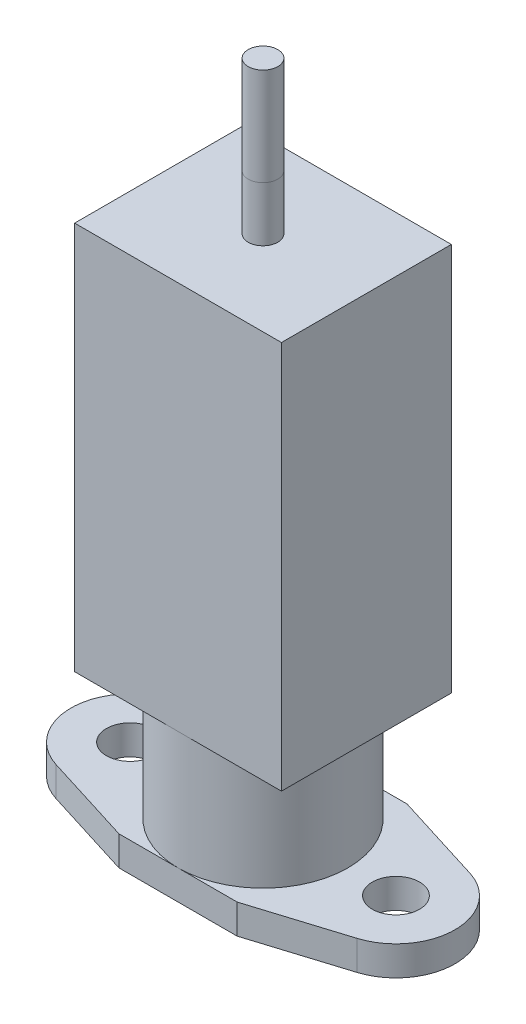
SolidWorks part; units mm, degrees
material "6061-T6 (SS)"
ref_plane "Front Plane" through (0, 0, 0) normal (0, 0, 1) x (1, 0, 0)
ref_plane "Top Plane" through (0, 0, 0) normal (0, 1, 0) x (1, 0, 0)
ref_plane "Right Plane" through (0, 0, 0) normal (1, 0, 0) x (0, 0, -1)
ref_axis "Axis1" through (0, 0, 55) along (0, 0, -1)
sketch "Sketch1" plane through (0, 0, 0) normal (0, 1, 0) x (1, 0, 0)
  line L0 (-9, 0) -> (9, 0) construction
  line L1 (-9, 4) -> (9, 4)
  line L2 (-9, -4) -> (9, -4)
  line L3 (4, -5.75) -> (10.1913, -3.8185)
  line L4 (-4, 5.75) -> (4, 5.75)
  line L5 (-4, 5.75) -> (-4, -5.75) construction
  line L6 (-4, -5.75) -> (4, -5.75)
  line L7 (4, 5.75) -> (4, -5.75) construction
  line L8 (-4, 5.75) -> (4, -5.75) construction
  line L9 (-4, -5.75) -> (4, 5.75) construction
  line L10 (-4, -5.75) -> (-10.1913, -3.8185)
  line L11 (-4, 5.75) -> (-10.1913, 3.8185)
  line L12 (4, 5.75) -> (10.1913, 3.8185)
  arc A0 (-9, 4) -> (-9, -4) centre (-9, 0) ccw
  arc A1 (9, -4) -> (9, 4) centre (9, 0) ccw
  circle A2 centre (9, 0) radius 1.6
  circle A3 centre (-9, 0) radius 1.6
  point P2 (0, 0)
  point P8 (0, 0)
  dimension "D3" = 3.2
  dimension "D4" = 4
  dimension "D1" = 18
  dimension "D2" = 11.5
  dimension "D5" = 8
extrude "Boss-Extrude1" add sketch "Sketch1" along normal blind 2 contours L2 A1 L1 A0 A3 A2 | A1 L12 L4 L11 A0 L1 | A1 L2 A0 L10 L6 L3 region at (0, 0, -4.7535) region at (0, 0, 0) region at (0, 0, 4.7535)
sketch "Sketch2" plane through (0, 2, 0) normal (0, 1, 0) x (1, 0, 0)
  circle A0 centre (0, 0) radius 5.75
extrude "Boss-Extrude2" add sketch "Sketch2" along normal blind 8
sketch "Sketch3" plane through (0, 10, 0) normal (0, 1, 0) x (1, 0, 0)
  line L0 (0, -5.75) -> (4, -5.75) construction
  line L1 (-7, 5.75) -> (7, 5.75)
  line L2 (-7, 5.75) -> (-7, -5.75)
  line L3 (-7, -5.75) -> (7, -5.75)
  line L4 (7, 5.75) -> (7, -5.75)
  line L5 (-7, 5.75) -> (7, -5.75) construction
  line L6 (-7, -5.75) -> (7, 5.75) construction
  point P0 (0, 0)
  dimension "D1" = 14
extrude "Boss-Extrude3" add sketch "Sketch3" along normal blind 26.3
sketch "Sketch4" plane through (0, 36.3, 0) normal (0, 1, 0) x (1, 0, 0)
  circle A0 centre (0, 0) radius 1
  dimension "D1" = 2
extrude "Boss-Extrude4" add sketch "Sketch4" along normal blind 3.7
extrude "Boss-Extrude5" add sketch "Sketch4<2>" along normal blind 6.6 from surface separate body starting at face at (0, 40, 1)
sketch "Sketch4<2>" plane through (0, 36.3, 0) normal (0, 1, 0) x (1, 0, 0) same geometry as "Sketch4"
